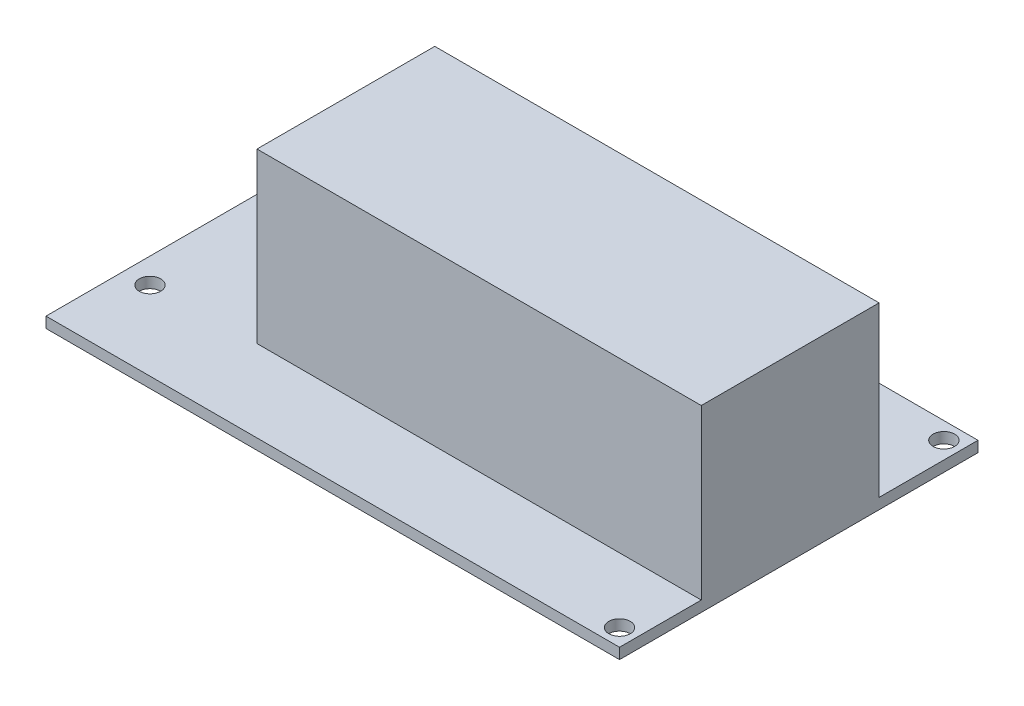
SolidWorks part; units mm, degrees
ref_plane "Front Plane" through (0, 0, 0) normal (0, 0, 1) x (1, 0, 0)
ref_plane "Top Plane" through (0, 0, 0) normal (0, 1, 0) x (1, 0, 0)
ref_plane "Right Plane" through (0, 0, 0) normal (1, 0, 0) x (0, 0, -1)
sketch "Sketch2" plane through (0, 0, 0) normal (0, 1, 0) x (1, 0, 0)
  line L1 (0, 0) -> (80, 0)
  line L2 (0, 0) -> (0, -50)
  line L3 (0, -50) -> (80, -50)
  line L4 (80, 0) -> (80, -50)
  line L5 (18.0294, -13.8) -> (80, -13.8)
  line L6 (18.0294, -13.8) -> (18.0294, -38.6)
  line L7 (18.0294, -38.6) -> (80, -38.6)
  line L8 (80, -13.8) -> (80, -38.6)
  circle A0 centre (3.5, -11) radius 1.5
  circle A1 centre (3.5, -39) radius 1.5
  circle A2 centre (77.62, -47.62) radius 1.5
  circle A3 centre (77.62, -2.38) radius 1.5
  dimension "D3" = 3
  dimension "D6" = 3
  dimension "D12" = 3
  dimension "D13" = 2.38
  dimension "D14" = 2.38
  dimension "D16" = 3
  dimension "D1" = 80
  dimension "D2" = 50
  dimension "D4" = 3.5
  dimension "D5" = 11
  dimension "D7" = 28
  dimension "D8" = 61.9706
  dimension "D9" = 24.8
  dimension "D10" = 13.8
  dimension "D11" = 2.38
  dimension "D15" = 2.38
extrude "Boss-Extrude1" add sketch "Sketch2" along normal blind 1.5 contours L4 L1 L2 L3 A0 L5 L8 L7 L6 region at (40, 0, 0.9434)
extrude "Boss-Extrude2" add sketch "Sketch2<3>" along normal blind 25 contours L8 L5 L6 L7 region at (49.0147, 0, 26.2)
sketch "Sketch2<3>" plane through (0, 0, 0) normal (0, 1, 0) x (1, 0, 0) same geometry as "Sketch2"
